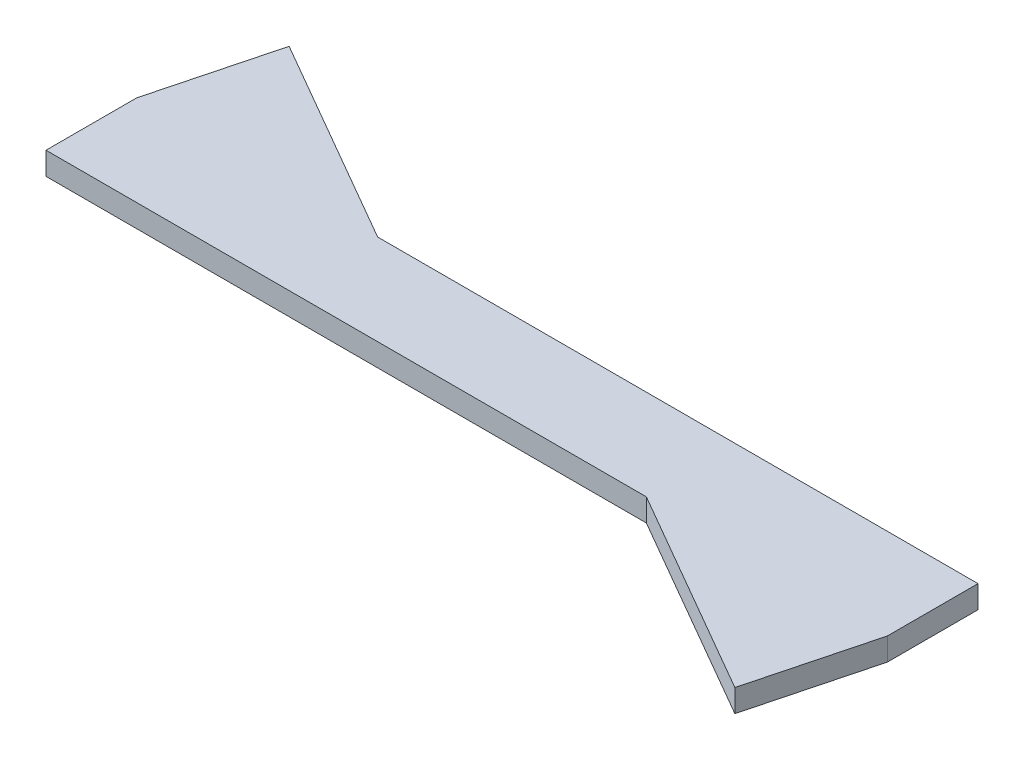
SolidWorks part; units mm, degrees
ref_plane "Front Plane" through (0, 0, 0) normal (0, 0, 1) x (1, 0, 0)
ref_plane "Top Plane" through (0, 0, 0) normal (0, 1, 0) x (1, 0, 0)
ref_plane "Right Plane" through (0, 0, 0) normal (1, 0, 0) x (0, 0, -1)
sketch "Sketch1" plane through (0, 0, 0) normal (0, 1, 0) x (1, 0, 0)
  line L0 (-88.3883, 9.525) -> (-88.5554, 7.8198)
  line L1 (-88.3883, -9.525) -> (88.3883, -9.525)
  line L2 (-88.3883, -9.525) -> (-88.3883, 9.525)
  line L3 (-88.3883, 9.525) -> (88.3883, 9.525)
  line L4 (88.3883, -9.525) -> (88.3883, 9.525)
  line L5 (-88.3883, -9.525) -> (88.3883, 9.525) construction
  line L6 (-88.3883, 9.525) -> (88.3883, -9.525) construction
  line L7 (-88.3883, 9.525) -> (-81.7524, 34.925)
  line L8 (-81.7524, 34.925) -> (-37.7583, 9.525)
  line L9 (-37.7583, 9.525) -> (-88.3883, 9.525)
  line L10 (88.3883, -9.525) -> (81.7524, -34.925)
  line L11 (81.7524, -34.925) -> (37.7583, -9.525)
  line L12 (37.7583, -9.525) -> (88.3883, -9.525)
  circle A0 centre (0, 0) radius 88.9
  dimension "D1" = 177.8
  dimension "D2" = 19.05
  dimension "D3" = 25.4
  dimension "D4" = 50.8
  dimension "D5" = 50.8
  dimension "D6" = 25.4
extrude "Boss-Extrude2" add sketch "Sketch1" along normal blind 4.7625 contours L8 L7 L3 | L1 L4 L3 L2 | L11 L10 L1 region at (0, 0, 0) region at (-69.2997, 0, -17.9917) region at (69.2997, 0, 17.9917)
